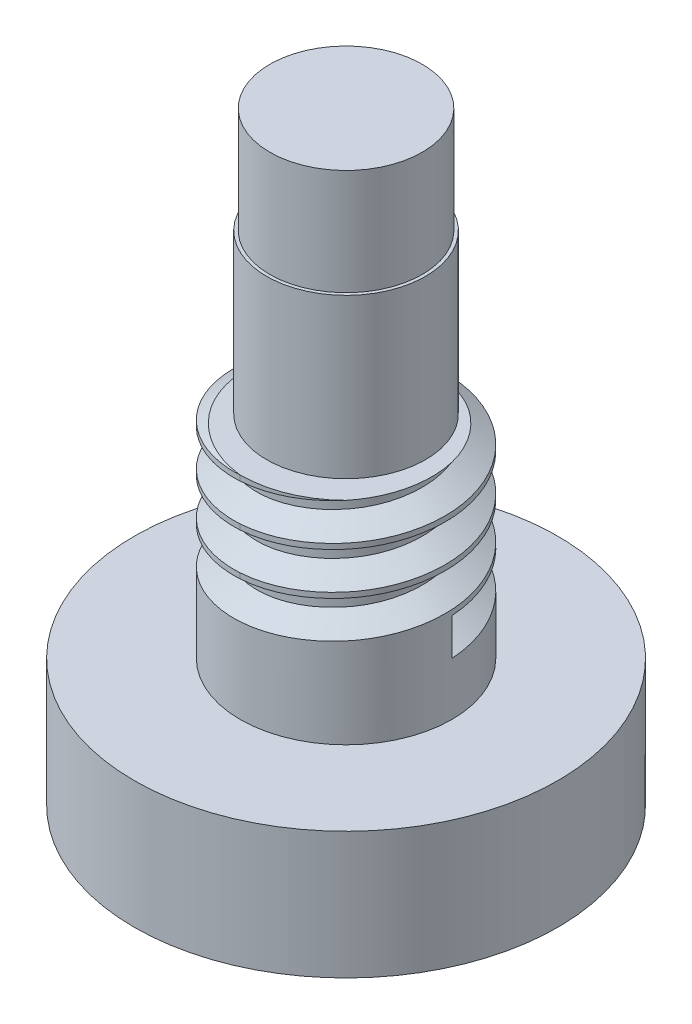
SolidWorks part; units mm, degrees
ref_plane "Front Plane" through (0, 0, 0) normal (0, 0, 1) x (1, 0, 0)
ref_plane "Top Plane" through (0, 0, 0) normal (0, 1, 0) x (1, 0, 0)
ref_plane "Right Plane" through (0, 0, 0) normal (1, 0, 0) x (0, 0, -1)
sketch "Sketch1" plane through (0, 0, 0) normal (0, 1, 0) x (1, 0, 0)
  circle A0 centre (0, 0) radius 2.286
  dimension "D1" = 4.572
extrude "Boss-Extrude1" add sketch "Sketch1" along normal blind 3.175
sketch "Sketch2" plane through (0, 0, 0) normal (0, -1, 0) x (-1, 0, 0)
  circle A0 centre (0, 0) radius 2.3825
  dimension "D1" = 4.765
extrude "Boss-Extrude2" add sketch "Sketch2" along normal blind 4.7622
sketch "Sketch3" plane through (0, -4.7622, 0) normal (0, -1, 0) x (-1, 0, 0)
  circle A0 centre (0, 0) radius 3.175
  dimension "D1" = 6.35
extrude "Boss-Extrude3" add sketch "Sketch3" along normal blind 3.175
sketch "Sketch4" plane through (0, -7.9372, 0) normal (0, -1, 0) x (-1, 0, 0)
  circle A0 centre (0, 0) radius 3.175
  dimension "D1" = 6.35
extrude "Boss-Extrude4" add sketch "Sketch4" along normal blind 3.175
thread "Thread2" pitch 1.27 method cut profile "Thread Profile3" start angle 0, offset 1.5875, length 0, pitch 1.27, diameter 6.35
ref_plane "Plane3" through (3.175, -9.5247, 0) normal (0, 0, 1) x (1, 0, 0)
sketch "Thread Profile3" plane through (3.175, -9.5247, 0) normal (0, 0, 1) x (1, 0, 0)
  line L0 (0, 0) -> (0, 1.27) construction
  line L11 (0, 0) -> (0, 1.1112)
  line L12 (0, 1.1112) -> (-0.6874, 0.7144)
  line L13 (-0.6874, 0.7144) -> (-0.6874, 0.3969)
  line L15 (-0.6874, 0.3969) -> (0, 0)
  line L17 (-0.6874, 0.5556) -> (0, 0.5556) construction
  point P2 (0, 0)
  dimension "Pitch" = 1.27
  dimension "Profile_Angle" = 60
  dimension "Profile_Land" = 0.3175
  dimension "Profile_Height" = 0.6874
sketch "Sketch11" plane through (0, -11.1122, 0) normal (0, -1, 0) x (-1, 0, 0)
  circle A0 centre (0, 0) radius 6.35
  dimension "D1" = 12.7
extrude "Boss-Extrude5" add sketch "Sketch11" along normal blind 3.81
fillet "Fillet1" [suppressed] radius 2.54
